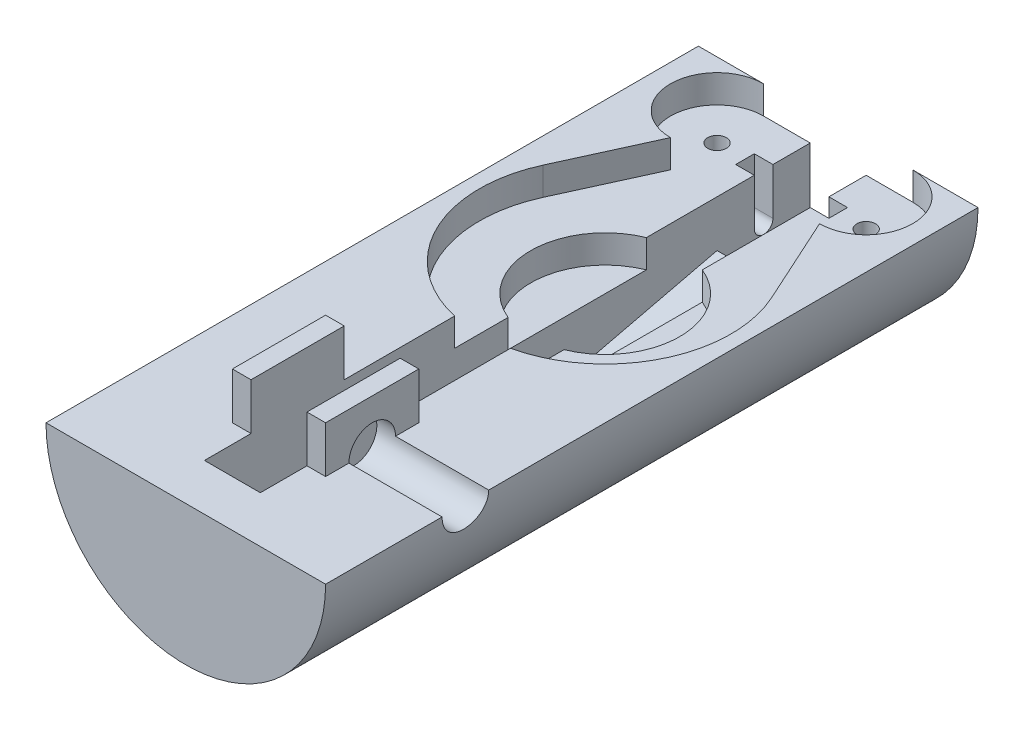
SolidWorks part; units mm, degrees
ref_plane "Alzado" through (0, 0, 0) normal (0, 0, 1) x (1, 0, 0)
ref_plane "Planta" through (0, 0, 0) normal (0, 1, 0) x (1, 0, 0)
ref_plane "Vista lateral" through (0, 0, 0) normal (1, 0, 0) x (0, 0, -1)
sketch "Croquis1" plane through (0, 0, 0) normal (0, 0, 1) x (1, 0, 0)
  line L0 (-15, 0) -> (15, 0)
  arc A1 (-15, 0) -> (15, 0) centre (0, 0) ccw
  dimension "D2" = 15
extrude "Saliente-Extruir1" add sketch "Croquis1" along normal blind 35 and the other way blind 35
sketch "Croquis3" plane through (0, 0, 0) normal (0, 1, 0) x (1, 0, 0)
  line L0 (0, 0) -> (0, 30) construction
  line L1 (-8, 25) -> (-12.2845, 15.5983)
  line L2 (0, 30) -> (0, 10) construction
  line L3 (8, 25) -> (12.2845, 15.5983)
  line L4 (-8, 35) -> (8, 35)
  line L8 (0, 30) -> (8, 30) construction
  line L9 (0, 30) -> (-8, 30) construction
  arc A0 (-8, 35) -> (-8, 25) centre (-8, 30) ccw
  arc A1 (8, 25) -> (8, 35) centre (8, 30) ccw
  arc A5 (-12.2845, 15.5983) -> (12.2845, 15.5983) centre (0, 10) ccw
  dimension "D6" = 10
  dimension "D8" = 27
  dimension "D1" = 30
  dimension "D2" = 20
  dimension "D4" = 8
  dimension "D5" = 8
extrude "Cortar-Extruir1" cut sketch "Croquis3" against normal blind 3
sketch "Croquis4" plane through (0, -3, 0) normal (0, 1, 0) x (1, 0, 0)
  circle A0 centre (0, 10) radius 8
  dimension "D1" = 16
extrude "Cortar-Extruir2" cut sketch "Croquis4" against normal blind 3
sketch "Croquis5" plane through (0, -6, 0) normal (0, 1, 0) x (1, 0, 0)
  circle A0 centre (0, 10) radius 2.5
  dimension "D1" = 5
extrude "Cortar-Extruir3" cut sketch "Croquis5" against normal blind 10
sketch "Croquis6" plane through (0, -3, 0) normal (0, 1, 0) x (1, 0, 0)
  line L0 (8, 35) -> (-8, 35) construction
  line L1 (-3, 25) -> (3, 25)
  line L2 (-3, 25) -> (-3, 35)
  line L3 (-3, 35) -> (3, 35)
  line L4 (3, 25) -> (3, 35)
  line L5 (-3, 25) -> (3, 35) construction
  line L6 (-3, 35) -> (3, 25) construction
  circle A0 centre (-8, 30) radius 1.5
  circle A1 centre (8, 30) radius 1.5
  point P6 (0, 30)
  dimension "D1" = 3
  dimension "D2" = 10
  dimension "D3" = 8
  dimension "D4" = 6
  dimension "D5" = 5
extrude "Cortar-Extruir5" cut sketch "Croquis6" against normal blind 10 contours L2 L3 L4 L1
sketch "Croquis7" plane through (0, -3, 0) normal (0, 1, 0) x (1, 0, 0)
  line L0 (-3, 30) -> (-5, 30) construction
  line L1 (-3, 25) -> (-3, 35) construction
  line L2 (3, 30) -> (5, 30) construction
  line L3 (3, 25) -> (3, 35) construction
  line L5 (-5, 31) -> (-3, 31)
  line L6 (-5, 31) -> (-5, 29)
  line L7 (-5, 29) -> (-3, 29)
  line L8 (-3, 31) -> (-3, 29)
  line L9 (-5, 31) -> (-3, 29) construction
  line L10 (-5, 29) -> (-3, 31) construction
  line L11 (3, 31) -> (5, 31)
  line L12 (3, 31) -> (3, 29)
  line L13 (3, 29) -> (5, 29)
  line L14 (5, 31) -> (5, 29)
  line L15 (3, 31) -> (5, 29) construction
  line L16 (3, 29) -> (5, 31) construction
  point P8 (-4, 30)
  point P13 (4, 30)
  dimension "D1" = 2
  dimension "D2" = 2
  dimension "D3" = 2
  dimension "D4" = 2
extrude "Cortar-Extruir6" cut sketch "Croquis7" against normal blind 5
sketch "Croquis8" plane through (0, -3, 0) normal (0, 1, 0) x (1, 0, 0)
  circle A0 centre (-8, 30) radius 1
  circle A1 centre (8, 30) radius 1
  dimension "D1" = 2
extrude "Cortar-Extruir7" cut sketch "Croquis8" against normal blind 2
sketch "Croquis9" plane through (0, -3, 0) normal (0, 1, 0) x (1, 0, 0)
  line L0 (0, 30) -> (0, 0) construction
  line L1 (15, 35) -> (-15, 35) construction
  line L3 (-3, 5) -> (3, 5)
  line L4 (-3, 5) -> (-3, -5)
  line L5 (-3, -5) -> (3, -5)
  line L6 (3, 5) -> (3, -5)
  line L7 (-3, 5) -> (3, -5) construction
  line L8 (-3, -5) -> (3, 5) construction
  point P3 (0, 35)
  dimension "D1" = 30
  dimension "D2" = 5
  dimension "D4" = 10
extrude "Cortar-Extruir8" cut sketch "Croquis9" against normal blind 12
sketch "Croquis10" plane through (0, 0, 0) normal (1, 0, 0) x (0, 0, -1)
  line L0 (29, -8) -> (31, -8) construction
  circle A0 centre (30, -8) radius 1
extrude "Cortar-Extruir9" cut sketch "Croquis10" against normal blind 5 and the other way blind 5
sketch "Croquis11" plane through (0, 0, 0) normal (1, 0, 0) x (0, 0, -1)
  line L0 (0, 0) -> (0, -12.5) construction
  line L1 (-6, -15) -> (6, -15)
  line L2 (1, -14) -> (6, -14)
  line L3 (-1, -14) -> (-1, -8)
  line L4 (-6, -14) -> (-1, -14)
  line L5 (1, -14) -> (1, -8)
  line L6 (30, -8) -> (-11.3011, -8) construction
  line L8 (-6, -14) -> (-6, -15)
  line L10 (6, -14) -> (6, -15)
  arc A0 (1, -8) -> (-1, -8) centre (0, -8) ccw
  point P8 (0, -15)
  dimension "D2" = 1
  dimension "D1" = 12.5
  dimension "D3" = 6
  dimension "D4" = 8
  dimension "D5" = 14
extrude "Cortar-Extruir10" cut sketch "Croquis11" against normal blind 5 and the other way blind 5
sketch "Croquis12" plane through (0, 0, 0) normal (1, 0, 0) x (0, 0, -1)
  line L0 (-20, -8) -> (-20, 0) construction
  line L1 (-3, -13) -> (-21.6588, -9.8615)
  line L2 (25, -8) -> (25, -3)
  line L3 (25, -3) -> (4, -3)
  line L4 (4, -13) -> (4, -3)
  line L5 (4, -13) -> (25, -8)
  line L6 (-3, 0) -> (-30, 0)
  line L7 (-3, 0) -> (-3, -13)
  line L8 (-3, -13) -> (-30, -13) construction
  line L9 (-30, 0) -> (-30, -13) construction
  line L10 (0, -8) -> (-20, -8) construction
  arc A0 (-30, 0) -> (-21.6588, -9.8615) centre (-20, 0) ccw
  dimension "D1" = 13
  dimension "D2" = 27
  dimension "D3" = 20
  dimension "D4" = 7
  dimension "D5" = 21
  dimension "D6" = 4
extrude "Cortar-Extruir11" cut sketch "Croquis12" against normal blind 3 and the other way blind 3
sketch "Croquis14" plane through (0, 0, 0) normal (0, 1, 0) x (1, 0, 0)
  line L0 (0, 10) -> (0, -20) construction
  line L1 (0, -3) -> (0, -30) construction
  line L3 (0, -20) -> (3, -20) construction
  line L4 (3, -21.6588) -> (3, -5) construction
  line L5 (3, -20) -> (3, -15) construction
  line L6 (3, -3.1624) -> (3, -30) construction
  line L7 (-3, -3.1624) -> (-3, -30) construction
  line L8 (3, -15) -> (5, -15)
  line L9 (3, -15) -> (3, -25)
  line L10 (3, -25) -> (5, -25)
  line L11 (5, -15) -> (5, -25)
  line L12 (-3, -15) -> (-5, -15)
  line L13 (-3, -15) -> (-3, -25)
  line L14 (-3, -25) -> (-5, -25)
  line L15 (-5, -15) -> (-5, -25)
  dimension "D1" = 30
  dimension "D2" = 5
  dimension "D3" = 10
  dimension "D4" = 10
  dimension "D5" = 5
  dimension "D6" = 2
  dimension "D7" = 2
extrude "Saliente-Extruir2" add sketch "Croquis14" along normal blind 5
sketch "Croquis15" plane through (0, 0, 0) normal (1, 0, 0) x (0, 0, -1)
  circle A0 centre (-20, 0) radius 2.5
  dimension "D1" = 5
extrude "Cortar-Extruir12" cut sketch "Croquis15" along normal blind 15
